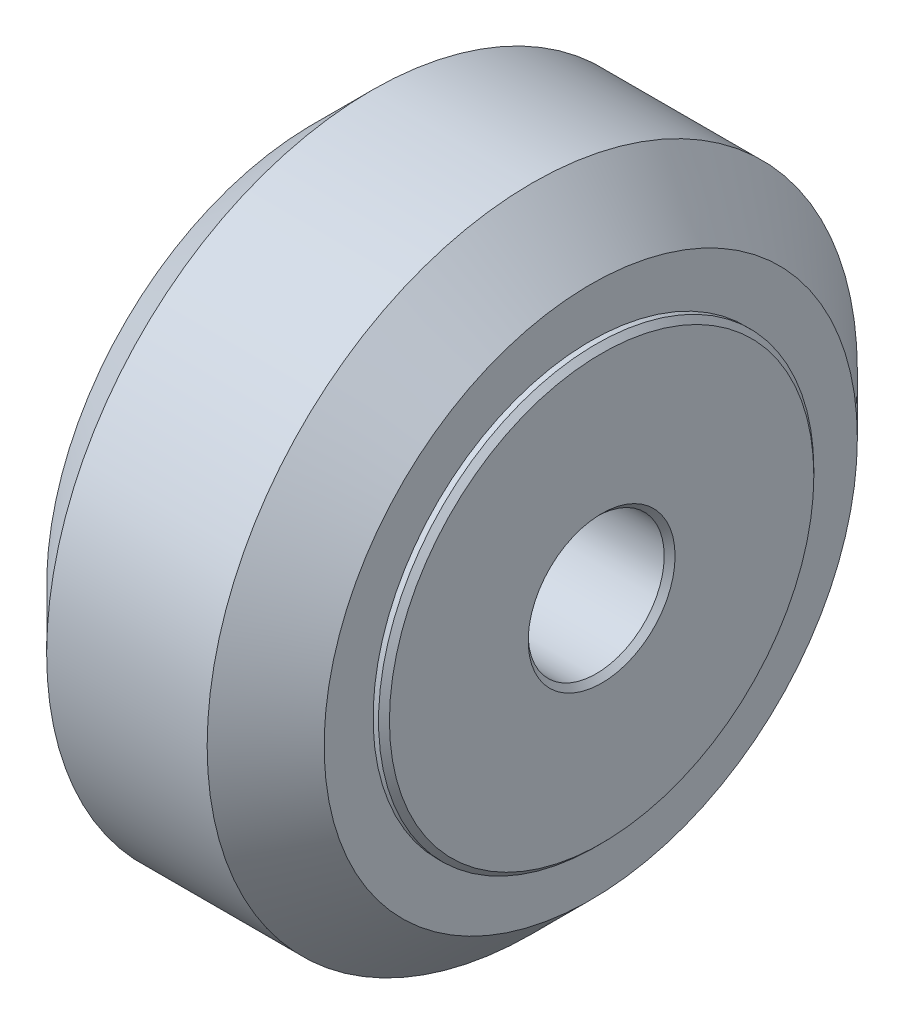
SolidWorks part; units mm, degrees
ref_plane "Front Plane" through (0, 0, 0) normal (0, 0, 1) x (1, 0, 0)
ref_plane "Top Plane" through (0, 0, 0) normal (0, 1, 0) x (1, 0, 0)
ref_plane "Right Plane" through (0, 0, 0) normal (1, 0, 0) x (0, 0, -1)
sketch "Sketch1" plane through (0, 0, 0) normal (0, 0, 1) x (1, 0, 0)
  line L0 (-0.5, 8) -> (-0.5, 7)
  line L1 (-0.5, 7) -> (0.5, 7)
  line L2 (0.5, 7) -> (0.5, 8)
  line L3 (0.5, 8) -> (5.1, 8)
  line L4 (5.1, 8) -> (5.1, 9.8)
  line L5 (5.1, 9.8) -> (2.95, 11.95)
  line L6 (2.95, 11.95) -> (-2.95, 11.95)
  line L7 (-2.95, 11.95) -> (-5.1, 9.8)
  line L8 (-5.1, 9.8) -> (-5.1, 8)
  line L9 (-5.1, 8) -> (-0.5, 8)
  line L10 (-5.1, 0) -> (5.1, 0) construction
revolve "Revolve1" add sketch "Sketch1" angle 360 about L10 reverse direction yes
sketch "Sketch2" plane through (0.5, 0, 0) normal (1, 0, 0) x (0, 0, -1)
  circle A0 centre (0, 0) radius 8
  circle A1 centre (0, 0) radius 2.5
  dimension "D1" = 16
  dimension "D2" = 5
extrude "bearing" add sketch "Sketch2" along normal blind 5 separate body
ref_plane "Plane1" through (0, 0, 0) normal (1, 0, 0) x (0, 0, -1)
sketch "Sketch3" plane through (0, 0, 0) normal (1, 0, 0) x (0, 0, -1)
  circle A0 centre (0, 0) radius 5
  circle A1 centre (0, 0) radius 2.5
  dimension "D1" = 10
  dimension "D2" = 5
extrude "Boss-Extrude1" add sketch "Sketch3" along normal mid plane 1 separate body
sketch "Sketch4" plane through (-0.5, 0, 0) normal (-1, 0, 0) x (0, 0, 1)
  circle A0 centre (0, 0) radius 8
  circle A1 centre (0, 0) radius 2.5
  dimension "D1" = 5
  dimension "D2" = 16
extrude "Boss-Extrude2" add sketch "Sketch4" along normal blind 5 separate body
chamfer "Chamfer1" distance 0.2 angle 45 2 edges at (5.5, 0, -8) (5.5, 0, -2.5)
chamfer "Chamfer2" distance 0.2 angle 45 2 edges at (-5.5, 0, 8) (-5.5, 0, 2.5)
